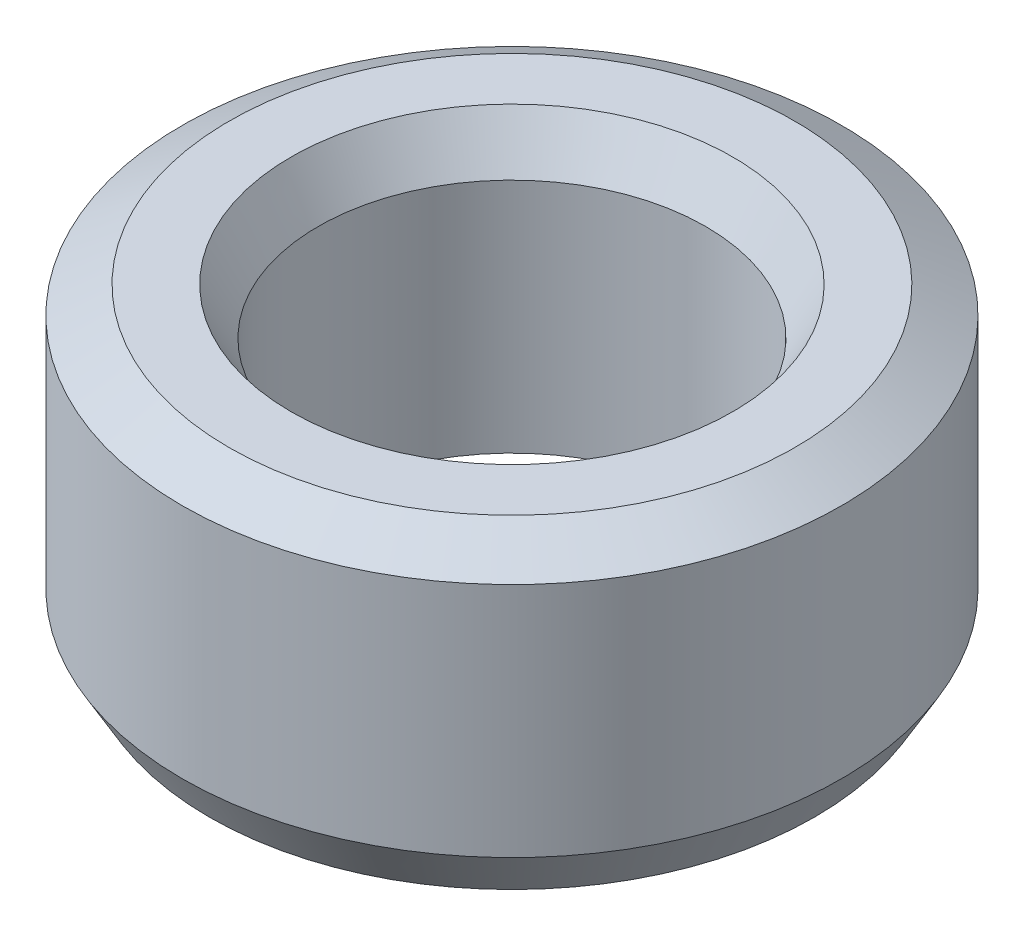
SolidWorks part; units mm, degrees
ref_plane "Front Plane" through (0, 0, 0) normal (0, 0, 1) x (1, 0, 0)
ref_plane "Top Plane" through (0, 0, 0) normal (0, 1, 0) x (1, 0, 0)
ref_plane "Right Plane" through (0, 0, 0) normal (1, 0, 0) x (0, 0, -1)
sketch "Sketch1" plane through (0, 0, 0) normal (0, 1, 0) x (1, 0, 0)
  circle A0 centre (0, 0) radius 37.5
  dimension "SLEEVE_OD" = 75
extrude "Boss-Extrude1" add sketch "Sketch1" along normal blind 35.2939
sketch "Sketch2" plane through (0, 0, 0) normal (0, 1, 0) x (1, 0, 0)
  circle A0 centre (0, 0) radius 22.0503
  dimension "BORE_D" = 44.1006
extrude "Cut-Extrude1" cut sketch "Sketch2" along normal through all
chamfer "Chamfer1" distance 3.0713 angle 60 4 edges at (0, 35.2939, 22.0503) (0, 0, 22.0503) (0, 0, 37.5) (0, 35.2939, 37.5) first distance on face at (0, 35.2939, 22.0503) first distance on face at (0, 0, 22.0503) first distance on face at (0, 35.2939, 37.5)
